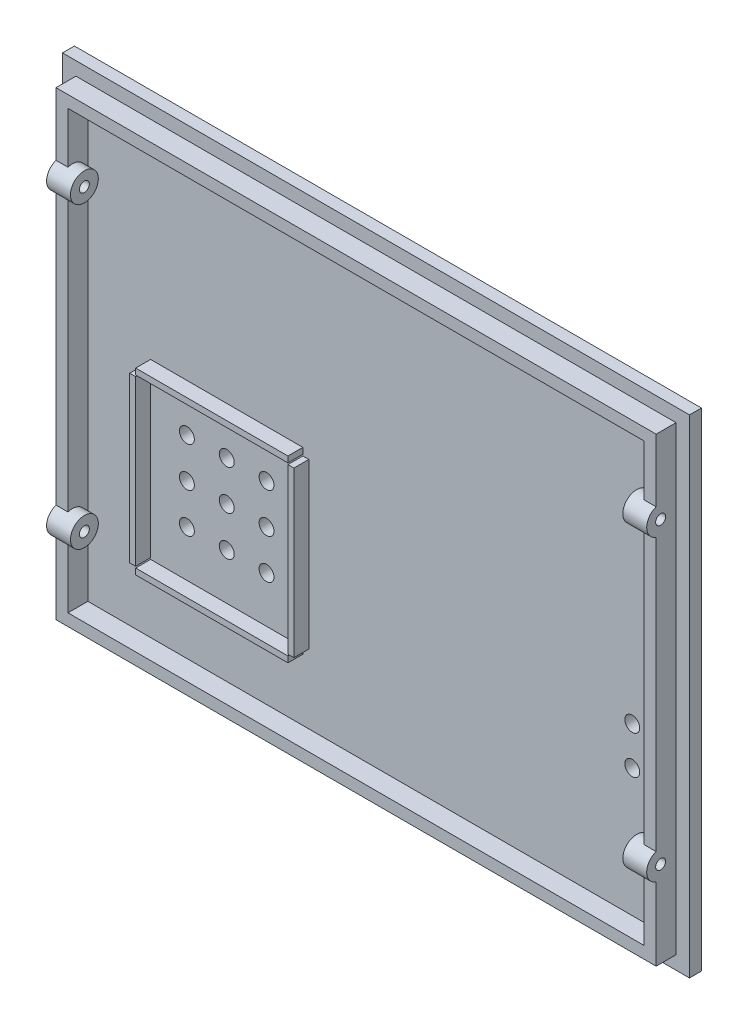
SolidWorks part; units mm, degrees
ref_plane "Front Plane" through (0, 0, 0) normal (0, 0, 1) x (1, 0, 0)
ref_plane "Top Plane" through (0, 0, 0) normal (0, 1, 0) x (1, 0, 0)
ref_plane "Right Plane" through (0, 0, 0) normal (1, 0, 0) x (0, 0, -1)
sketch "Sketch1" plane through (0, 0, 0) normal (0, 0, 1) x (1, 0, 0)
  line L1 (-63, 60) -> (63, 60)
  line L2 (-63, 60) -> (-63, 158)
  line L3 (-63, 158) -> (63, 158)
  line L4 (63, 60) -> (63, 158)
extrude "Boss-Extrude1" add sketch "Sketch1" along normal blind 2.4 from offset 36
sketch "Sketch2" plane through (0, 0, 0) normal (0, 0, 1) x (1, 0, 0)
  line L1 (-60.3, 62.7) -> (60.3, 62.7)
  line L2 (-60.3, 62.7) -> (-60.3, 155.3)
  line L3 (-60.3, 155.3) -> (60.3, 155.3)
  line L4 (60.3, 62.7) -> (60.3, 155.3)
extrude "Boss-Extrude2" add sketch "Sketch2" along normal blind 4.5 from offset 37.9
sketch "Sketch3" plane through (0, 0, 0) normal (0, 0, 1) x (1, 0, 0)
  line L1 (-57.9, 65.1) -> (57.9, 65.1)
  line L2 (-57.9, 65.1) -> (-57.9, 152.9)
  line L3 (-57.9, 152.9) -> (57.9, 152.9)
  line L4 (57.9, 65.1) -> (57.9, 152.9)
extrude "Boss-Extrude3" add sketch "Sketch3" along normal blind 5 from offset 38.4 separate body
combine bodies "Combine1" operation type subtract main body 102 bodies to subtract 103
sketch "Sketch4" plane through (0, 0, 0) normal (1, 0, 0) x (0, 0, -1)
  circle A0 centre (-41.5, 80) radius 2.8
extrude "Boss-Extrude4" add sketch "Sketch4" along normal blind 4.8 from offset 60.3 offset against normal yes
sketch "Sketch5" plane through (0, 0, 0) normal (1, 0, 0) x (0, 0, -1)
  circle A0 centre (-41.5, 80) radius 1
extrude "Boss-Extrude5" add sketch "Sketch5" along normal blind 6.5 from offset 61 separate body offset against normal yes
combine bodies "Combine2" operation type subtract main body 105 bodies to subtract 106
sketch "Sketch6" plane through (0, 0, 0) normal (1, 0, 0) x (0, 0, -1)
  circle A0 centre (-41.5, 140) radius 2.8
extrude "Boss-Extrude6" add sketch "Sketch6" along normal blind 4.8 from offset 60.3 offset against normal yes
sketch "Sketch7" plane through (0, 0, 0) normal (1, 0, 0) x (0, 0, -1)
  circle A0 centre (-41.5, 140) radius 1
extrude "Boss-Extrude7" add sketch "Sketch7" along normal blind 6.5 from offset 61 separate body offset against normal yes
combine bodies "Combine3" operation type subtract main body 108 bodies to subtract 109
sketch "Sketch8" plane through (0, 0, 0) normal (1, 0, 0) x (0, 0, -1)
  circle A0 centre (-41.5, 80) radius 2.8
extrude "Boss-Extrude8" add sketch "Sketch8" along normal blind 4.8 from offset 55.5
sketch "Sketch9" plane through (0, 0, 0) normal (1, 0, 0) x (0, 0, -1)
  circle A0 centre (-41.5, 80) radius 1
extrude "Boss-Extrude9" add sketch "Sketch9" along normal blind 6.5 from offset 54.5 separate body
combine bodies "Combine4" operation type subtract main body 111 bodies to subtract 112
sketch "Sketch10" plane through (0, 0, 0) normal (1, 0, 0) x (0, 0, -1)
  circle A0 centre (-41.5, 140) radius 2.8
extrude "Boss-Extrude10" add sketch "Sketch10" along normal blind 4.8 from offset 55.5
sketch "Sketch11" plane through (0, 0, 0) normal (1, 0, 0) x (0, 0, -1)
  circle A0 centre (-41.5, 140) radius 1
extrude "Boss-Extrude11" add sketch "Sketch11" along normal blind 6.5 from offset 54.5 separate body
combine bodies "Combine5" operation type subtract main body 114 bodies to subtract 115
sketch "Sketch12" plane through (0, 0, 0) normal (0, 0, 1) x (1, 0, 0)
  circle A0 centre (-38, 88) radius 1.5
extrude "Boss-Extrude12" add sketch "Sketch12" along normal blind 4.4 from offset 35 separate body
combine bodies "Combine6" operation type subtract main body 116 bodies to subtract 117
sketch "Sketch13" plane through (0, 0, 0) normal (0, 0, 1) x (1, 0, 0)
  circle A0 centre (-38, 96) radius 1.5
extrude "Boss-Extrude13" add sketch "Sketch13" along normal blind 4.4 from offset 35 separate body
combine bodies "Combine7" operation type subtract main body 118 bodies to subtract 119
sketch "Sketch14" plane through (0, 0, 0) normal (0, 0, 1) x (1, 0, 0)
  circle A0 centre (-38, 104) radius 1.5
extrude "Boss-Extrude14" add sketch "Sketch14" along normal blind 4.4 from offset 35 separate body
combine bodies "Combine8" operation type subtract main body 120 bodies to subtract 121
sketch "Sketch15" plane through (0, 0, 0) normal (0, 0, 1) x (1, 0, 0)
  circle A0 centre (-30, 88) radius 1.5
extrude "Boss-Extrude15" add sketch "Sketch15" along normal blind 4.4 from offset 35 separate body
combine bodies "Combine9" operation type subtract main body 122 bodies to subtract 123
sketch "Sketch16" plane through (0, 0, 0) normal (0, 0, 1) x (1, 0, 0)
  circle A0 centre (-30, 96) radius 1.5
extrude "Boss-Extrude16" add sketch "Sketch16" along normal blind 4.4 from offset 35 separate body
combine bodies "Combine10" operation type subtract main body 124 bodies to subtract 125
sketch "Sketch17" plane through (0, 0, 0) normal (0, 0, 1) x (1, 0, 0)
  circle A0 centre (-30, 104) radius 1.5
extrude "Boss-Extrude17" add sketch "Sketch17" along normal blind 4.4 from offset 35 separate body
combine bodies "Combine11" operation type subtract main body 126 bodies to subtract 127
sketch "Sketch18" plane through (0, 0, 0) normal (0, 0, 1) x (1, 0, 0)
  circle A0 centre (-22, 88) radius 1.5
extrude "Boss-Extrude18" add sketch "Sketch18" along normal blind 4.4 from offset 35 separate body
combine bodies "Combine12" operation type subtract main body 128 bodies to subtract 129
sketch "Sketch19" plane through (0, 0, 0) normal (0, 0, 1) x (1, 0, 0)
  circle A0 centre (-22, 96) radius 1.5
extrude "Boss-Extrude19" add sketch "Sketch19" along normal blind 4.4 from offset 35 separate body
combine bodies "Combine13" operation type subtract main body 130 bodies to subtract 131
sketch "Sketch20" plane through (0, 0, 0) normal (0, 0, 1) x (1, 0, 0)
  circle A0 centre (-22, 104) radius 1.5
extrude "Boss-Extrude20" add sketch "Sketch20" along normal blind 4.4 from offset 35 separate body
combine bodies "Combine14" operation type subtract main body 132 bodies to subtract 133
sketch "Sketch21" plane through (0, 0, 0) normal (0, 0, 1) x (1, 0, 0)
  line L1 (-46.5, 79) -> (-45.3, 79)
  line L2 (-46.5, 79) -> (-46.5, 112)
  line L3 (-46.5, 112) -> (-45.3, 112)
  line L4 (-45.3, 79) -> (-45.3, 112)
extrude "Boss-Extrude21" add sketch "Sketch21" along normal blind 3 from offset 38.4
sketch "Sketch22" plane through (0, 0, 0) normal (0, 0, 1) x (1, 0, 0)
  line L1 (-14.7, 79) -> (-13.5, 79)
  line L2 (-14.7, 79) -> (-14.7, 112)
  line L3 (-14.7, 112) -> (-13.5, 112)
  line L4 (-13.5, 79) -> (-13.5, 112)
extrude "Boss-Extrude22" add sketch "Sketch22" along normal blind 3 from offset 38.4
sketch "Sketch23" plane through (0, 0, 0) normal (0, 0, 1) x (1, 0, 0)
  line L1 (-45.3, 112.3) -> (-14.7, 112.3)
  line L2 (-45.3, 112.3) -> (-45.3, 113.5)
  line L3 (-45.3, 113.5) -> (-14.7, 113.5)
  line L4 (-14.7, 112.3) -> (-14.7, 113.5)
extrude "Boss-Extrude23" add sketch "Sketch23" along normal blind 3 from offset 38.4
sketch "Sketch24" plane through (0, 0, 0) normal (0, 0, 1) x (1, 0, 0)
  line L1 (-45.3, 77.5) -> (-14.7, 77.5)
  line L2 (-45.3, 77.5) -> (-45.3, 78.7)
  line L3 (-45.3, 78.7) -> (-14.7, 78.7)
  line L4 (-14.7, 77.5) -> (-14.7, 78.7)
extrude "Boss-Extrude24" add sketch "Sketch24" along normal blind 3 from offset 38.4
sketch "Sketch25" plane through (0, 0, 0) normal (0, 0, 1) x (1, 0, 0)
  circle A0 centre (51.5, 98.5) radius 1.5
extrude "Boss-Extrude25" add sketch "Sketch25" along normal blind 4.4 from offset 35 separate body
combine bodies "Combine15" operation type subtract main body 138 bodies to subtract 139
sketch "Sketch26" plane through (0, 0, 0) normal (0, 0, 1) x (1, 0, 0)
  circle A0 centre (51.5, 90.8) radius 1.5
extrude "Boss-Extrude26" add sketch "Sketch26" along normal blind 4.4 from offset 35 separate body
combine bodies "Combine16" operation type subtract main body 140 bodies to subtract 141
